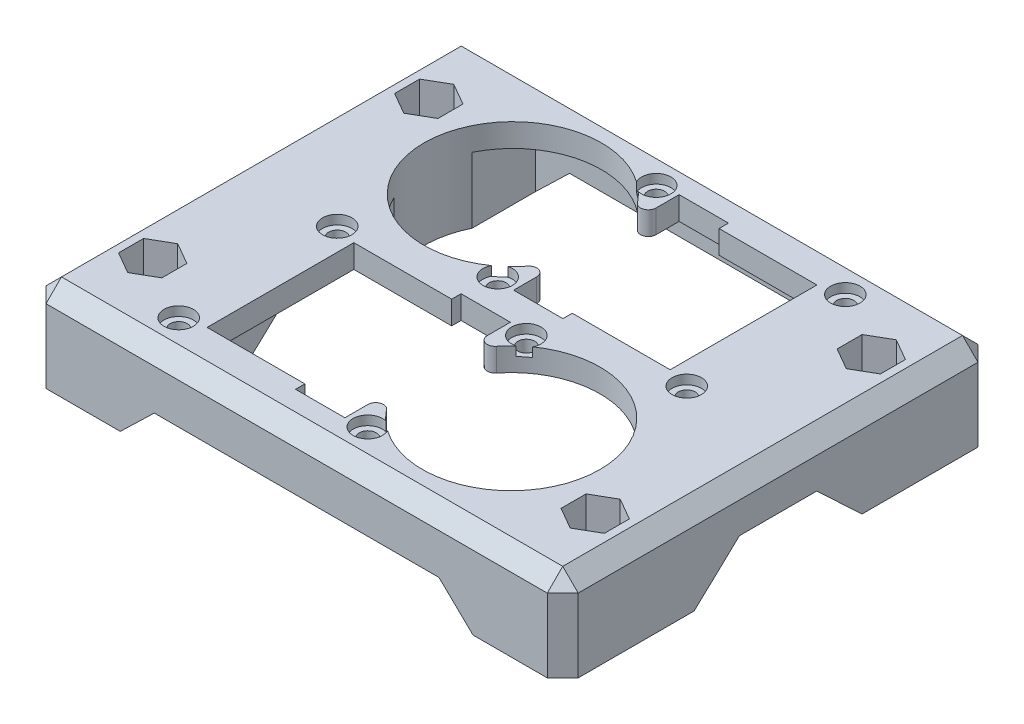
SolidWorks part; units mm, degrees
ref_plane "Plan de face" through (0, 0, 0) normal (0, 0, 1) x (1, 0, 0)
ref_plane "Plan de dessus" through (0, 0, 0) normal (0, 1, 0) x (1, 0, 0)
ref_plane "Plan de droite" through (0, 0, 0) normal (1, 0, 0) x (0, 0, -1)
sketch "Esquisse1" plane through (0, 0, 0) normal (0, 1, 0) x (1, 0, 0)
  line L0 (0, 0) -> (0, 20.5) construction
  line L1 (0, 20.5) -> (24.45, 20.5) construction
  line L2 (24.45, 20.5) -> (24.45, 0) construction
  line L3 (24.45, 0) -> (0, 0) construction
  line L4 (-16.05, -25.2) -> (-16.05, -4.7) construction
  line L5 (-16.05, -4.7) -> (8.4, -4.7) construction
  line L6 (8.4, -4.7) -> (8.4, -25.2) construction
  line L7 (8.4, -25.2) -> (-16.05, -25.2) construction
  line L8 (8.89, 19.74) -> (21.54, 19.74)
  line L9 (21.54, 19.74) -> (21.54, 0.76)
  line L10 (21.54, 0.76) -> (8.89, 0.76)
  line L11 (-0.49, -4.25) -> (5.89, -4.25)
  line L12 (2.51, 20.95) -> (8.89, 20.95)
  line L13 (2.51, 20.95) -> (2.51, -0.45)
  line L14 (2.51, -0.45) -> (8.89, -0.45)
  line L15 (8.89, 20.95) -> (8.89, -0.45)
  line L16 (-0.49, -4.25) -> (-0.49, -25.65)
  line L17 (-0.49, -25.65) -> (5.89, -25.65)
  line L18 (5.89, -4.25) -> (5.89, -25.65)
  line L19 (-0.49, -5.46) -> (-13.14, -5.46)
  line L20 (-13.14, -5.46) -> (-13.14, -24.44)
  line L21 (-13.14, -24.44) -> (-0.49, -24.44)
  line L22 (-21.05, 23.5) -> (-21.05, -28.2)
  line L23 (-21.05, -28.2) -> (29.45, -28.2)
  line L24 (29.45, -28.2) -> (29.45, 23.5)
  line L25 (29.45, 23.5) -> (-21.05, 23.5)
  circle A0 centre (0, 0) radius 1.1
  circle A1 centre (24.45, 0) radius 1.1
  circle A2 centre (24.45, 20.5) radius 1.1
  circle A3 centre (0, 20.5) radius 1.1
  circle A4 centre (-16.05, -25.2) radius 1.1
  circle A5 centre (8.4, -25.2) radius 1.1
  circle A6 centre (8.4, -4.7) radius 1.1
  circle A7 centre (-16.05, -4.7) radius 1.1
  circle A8 centre (-8.3, 10.25) radius 11.48
  circle A9 centre (16.7, -14.95) radius 11.48
  point P17 (21.54, 10.25)
  point P22 (24.45, 10.25)
  point P28 (8.89, 10.25)
  point P31 (0, 10.25)
  point P34 (8.4, -14.95)
  point P39 (5.89, -14.95)
  point P45 (-13.14, -14.95)
  point P46 (-16.05, -14.95)
  dimension "D1" = 2.2
  dimension "D4" = 2.2
  dimension "D14" = 22.96
  dimension "D2" = 20.5
  dimension "D3" = 24.45
  dimension "D5" = 20.5
  dimension "D6" = 24.45
  dimension "D7" = 4.7
  dimension "D8" = 8.4
  dimension "D9" = 18.98
  dimension "D10" = 12.65
  dimension "D11" = 6.38
  dimension "D12" = 21.4
  dimension "D13" = 2.91
  dimension "D15" = 8.3
  dimension "D16" = 8.3
  dimension "D17" = 2.91
  dimension "D18" = 18.98
  dimension "D19" = 12.65
  dimension "D20" = 3
  dimension "D21" = 5
  dimension "D22" = 3
  dimension "D23" = 5
extrude "Boss.-Extru.1" add sketch "Esquisse1" along normal blind 3 contours L24 L25 L22 L23 A9 L18 L17 L16 L21 L20 L19 L11 A8 L13 L12 L15 L8 L9 L10 L14 A7 A6 A5 A4 A3 A2 A1 A0 region at (4.2, 0, 2.35)
fillet "Congé1" radius 1 4 edges at (2.51, 1.5, -14.1145) (2.51, 1.5, -6.3855) (5.89, 1.5, 18.8145) (5.89, 1.5, 11.0855)
hole_wizard "Chambrage pour vis à six pans creux M1.61" positions "Esquisse2" profile "Esquisse3" counterbore size "M1.6" standard "ISO" end condition through all
sketch "Esquisse2" plane through (0, 3, 0) normal (0, 1, 0) x (1, 0, 0)
  point P0 (-16.05, -4.7)
  point P3 (-16.05, -25.2)
  point P6 (8.4, -25.2)
  point P9 (8.4, -4.7)
  point P12 (0, 0)
  point P15 (0, 20.5)
  point P18 (24.45, 20.5)
  point P21 (24.45, 0)
sketch "Esquisse3" plane through (-16.05, 3, 4.7) normal (1, 0, 0) x (0, 0, 1)
  line L0 (0, 0) -> (0, 3)
  line L1 (0, 3) -> (1.1, 3)
  line L3 (1.1, 3) -> (1.1, 1.2)
  line L4 (1.1, 1.2) -> (1.9, 1.2)
  line L5 (1.9, 1.2) -> (1.9, 0)
  line L7 (1.9, 0) -> (0, 0)
  line L11 (0, -6.35) -> (0, 107.95) construction
  dimension "Diamètre du perçage jusqu'au prochain" = 2.2
  dimension "Profondeur du perçage jusqu'au prochain" = 3
  dimension "Diamètre du chambrage" = 3.8
  dimension "Profondeur du chambrage" = 1.2
sketch "Esquisse4" plane through (0, 3, 0) normal (0, 1, 0) x (1, 0, 0)
  line L0 (-21.05, 23.5) -> (-21.05, -28.2) construction
  line L1 (-18.61, 23.5) -> (-30.21, 23.5)
  line L2 (-18.61, 23.5) -> (-18.61, 15.2992)
  line L3 (-18.61, -28.2) -> (-30.21, -28.2)
  line L4 (-30.21, 23.5) -> (-30.21, -28.2)
  line L5 (29.45, 23.5) -> (-21.05, 23.5) construction
  line L6 (27.01, 23.5) -> (38.61, 23.5)
  line L7 (27.01, 23.5) -> (27.01, -9.9008)
  line L8 (27.01, -28.2) -> (38.61, -28.2)
  line L9 (38.61, 23.5) -> (38.61, -28.2)
  line L10 (29.45, -28.2) -> (29.45, 23.5) construction
  line L11 (-21.05, -28.2) -> (29.45, -28.2) construction
  line L12 (-18.61, 15.2992) -> (-18.61, 5.2008) construction
  line L13 (-18.61, 5.2008) -> (-18.61, -28.2)
  line L14 (27.01, -9.9008) -> (27.01, -19.9992) construction
  line L15 (27.01, -19.9992) -> (27.01, -28.2)
  line L16 (-30.21, 15.5) -> (-18.61, 15.5) construction
  line L17 (-30.21, -2.35) -> (-56.6243, -2.35) construction
  line L18 (4.2, 23.5) -> (4.2, 41.2903) construction
  arc A0 (-1.6935, 19.6385) -> (-1.6935, 0.8615) centre (-8.3, 10.25) ccw construction
  arc A1 (-18.61, 15.2992) -> (-18.61, 5.2008) centre (-8.3, 10.25) ccw
  arc A2 (10.0935, -24.3385) -> (10.0935, -5.5615) centre (16.7, -14.95) ccw construction
  arc A3 (27.01, -19.9992) -> (27.01, -9.9008) centre (16.7, -14.95) ccw
  arc A4 (27.01, -9.9008) -> (10.0935, -5.5615) centre (16.7, -14.95) ccw construction
  arc A5 (10.0935, -24.3385) -> (27.01, -19.9992) centre (16.7, -14.95) ccw construction
  arc A6 (-18.61, 5.2008) -> (-1.6935, 0.8615) centre (-8.3, 10.25) ccw construction
  arc A7 (-1.6935, 19.6385) -> (-18.61, 15.2992) centre (-8.3, 10.25) ccw construction
  circle A8 centre (-24.41, 15.5) radius 1.6
  circle A9 centre (-24.41, -20.2) radius 1.6
  circle A10 centre (32.81, 15.5) radius 1.6
  circle A11 centre (32.81, -20.2) radius 1.6
  point P32 (-24.41, 15.5)
  dimension "D5" = 3.2
  dimension "D1" = 9.16
  dimension "D2" = 11.6
  dimension "D3" = 9.16
  dimension "D4" = 11.6
  dimension "D6" = 8
extrude "Boss.-Extru.2" add sketch "Esquisse4" against normal blind 19
sketch "Esquisse5" plane through (0, -16, 0) normal (0, -1, 0) x (1, 0, 0)
  line L1 (-24.41, 23.4332) -> (-27.21, 21.8166)
  line L2 (-27.21, 21.8166) -> (-27.21, 18.5834)
  line L3 (-27.21, 18.5834) -> (-24.41, 16.9668)
  line L4 (-24.41, 16.9668) -> (-21.61, 18.5834)
  line L5 (-21.61, 18.5834) -> (-21.61, 21.8166)
  line L6 (-21.61, 21.8166) -> (-24.41, 23.4332)
  line L7 (-24.41, -12.2668) -> (-27.21, -13.8834)
  line L8 (-27.21, -13.8834) -> (-27.21, -17.1166)
  line L9 (-27.21, -17.1166) -> (-24.41, -18.7332)
  line L10 (-24.41, -18.7332) -> (-21.61, -17.1166)
  line L11 (-21.61, -17.1166) -> (-21.61, -13.8834)
  line L12 (-21.61, -13.8834) -> (-24.41, -12.2668)
  line L13 (32.81, -12.2668) -> (30.01, -13.8834)
  line L14 (30.01, -13.8834) -> (30.01, -17.1166)
  line L15 (30.01, -17.1166) -> (32.81, -18.7332)
  line L16 (32.81, -18.7332) -> (35.61, -17.1166)
  line L17 (35.61, -17.1166) -> (35.61, -13.8834)
  line L18 (35.61, -13.8834) -> (32.81, -12.2668)
  line L19 (32.81, 23.4332) -> (30.01, 21.8166)
  line L20 (30.01, 21.8166) -> (30.01, 18.5834)
  line L21 (30.01, 18.5834) -> (32.81, 16.9668)
  line L22 (32.81, 16.9668) -> (35.61, 18.5834)
  line L23 (35.61, 18.5834) -> (35.61, 21.8166)
  line L24 (35.61, 21.8166) -> (32.81, 23.4332)
  circle A0 centre (-24.41, 20.2) radius 2.8 construction
  circle A1 centre (-24.41, -15.5) radius 2.8 construction
  circle A2 centre (32.81, -15.5) radius 2.8 construction
  circle A3 centre (32.81, 20.2) radius 2.8 construction
  dimension "D1" = 5.6
extrude "Enlèv. mat.-Extru.1" cut sketch "Esquisse5" along normal blind 7 from surface starting at face at (4.2, 3, 2.35)
sketch "Esquisse6" plane through (38.61, 0, 0) normal (1, 0, 0) x (0, 0, -1)
  line L0 (-28.2, -8.5) -> (-13.2, -8.5)
  line L1 (-28.2, -16) -> (-28.2, 3) construction
  line L2 (-13.2, -8.5) -> (-7.35, -3)
  line L3 (-7.35, -3) -> (2.65, -3)
  line L4 (-2.35, -16) -> (-2.35, -24.1337) construction
  line L5 (-28.2, -16) -> (23.5, -16) construction
  line L6 (-28.2, 3) -> (23.5, 3) construction
  line L7 (8.5, -8.5) -> (2.65, -3)
  line L8 (23.5, -8.5) -> (8.5, -8.5)
  line L9 (23.5, -16) -> (23.5, 3) construction
  line L10 (23.5, -16) -> (23.5, -8.5)
  line L11 (-28.2, -16) -> (23.5, -16)
  line L12 (-28.2, -16) -> (-28.2, -8.5)
  point P14 (-2.35, -3)
  dimension "D1" = 7.5
  dimension "D2" = 5
  dimension "D3" = 15
  dimension "D4" = 6
extrude "Enlèv. mat.-Extru.2" cut sketch "Esquisse6" against normal through all both and the other way through all
ref_plane "Plan1" through (0, 0, 2.35) normal (0, 0, 1) x (1, 0, 0)
sketch "Esquisse7" plane through (0, 0, 28.2) normal (0, 0, 1) x (1, 0, 0)
  line L0 (-18.61, -8.5) -> (-14.205, -4.25)
  line L1 (-18.61, 0) -> (27.01, 0) construction
  line L2 (-14.205, -4.25) -> (22.605, -4.25)
  line L5 (4.2, 3) -> (4.2, 15.4308) construction
  line L6 (-30.21, 3) -> (38.61, 3) construction
  line L7 (27.01, -8.5) -> (22.605, -4.25)
  line L8 (-9.8, 0) -> (18.2, 0) construction
  line L9 (22.605, -4.25) -> (18.2, 0) construction
  line L10 (-14.205, -4.25) -> (-9.8, 0) construction
  line L15 (-30.21, 3) -> (-30.21, -8.5)
  line L16 (-30.21, -8.5) -> (-18.61, -8.5)
  line L17 (-18.61, -8.5) -> (-18.61, 0)
  line L18 (-18.61, 0) -> (27.01, 0)
  line L19 (27.01, 0) -> (27.01, -8.5)
  line L20 (27.01, -8.5) -> (38.61, -8.5)
  line L21 (38.61, -8.5) -> (38.61, 3)
  line L22 (38.61, 3) -> (-30.21, 3)
  line L23 (-30.21, 3) -> (-30.21, -8.5)
  line L24 (-30.21, -8.5) -> (-18.61, -8.5)
  line L28 (27.01, -8.5) -> (38.61, -8.5)
  line L29 (38.61, -8.5) -> (38.61, 3)
  line L30 (38.61, 3) -> (-30.21, 3)
  dimension "D2" = 28
  dimension "D3" = 7.25
  dimension "D1" = 0
extrude "Boss.-Extru.3" add sketch "Esquisse7" along normal blind 2
mirror "Symétrie1" about plane through (0, 0, 2.35) normal (0, 0, 1) of "Boss.-Extru.3"
chamfer "Chanfrein1" distance 2 angle 45 8 edges at (-30.21, 3, 2.35) (38.61, 3, 2.35) (38.61, -2.75, -25.5) (38.61, -2.75, 30.2) (-30.21, -2.75, 30.2) (-30.21, -2.75, -25.5) (4.2, 3, -25.5) (4.2, 3, 30.2)
